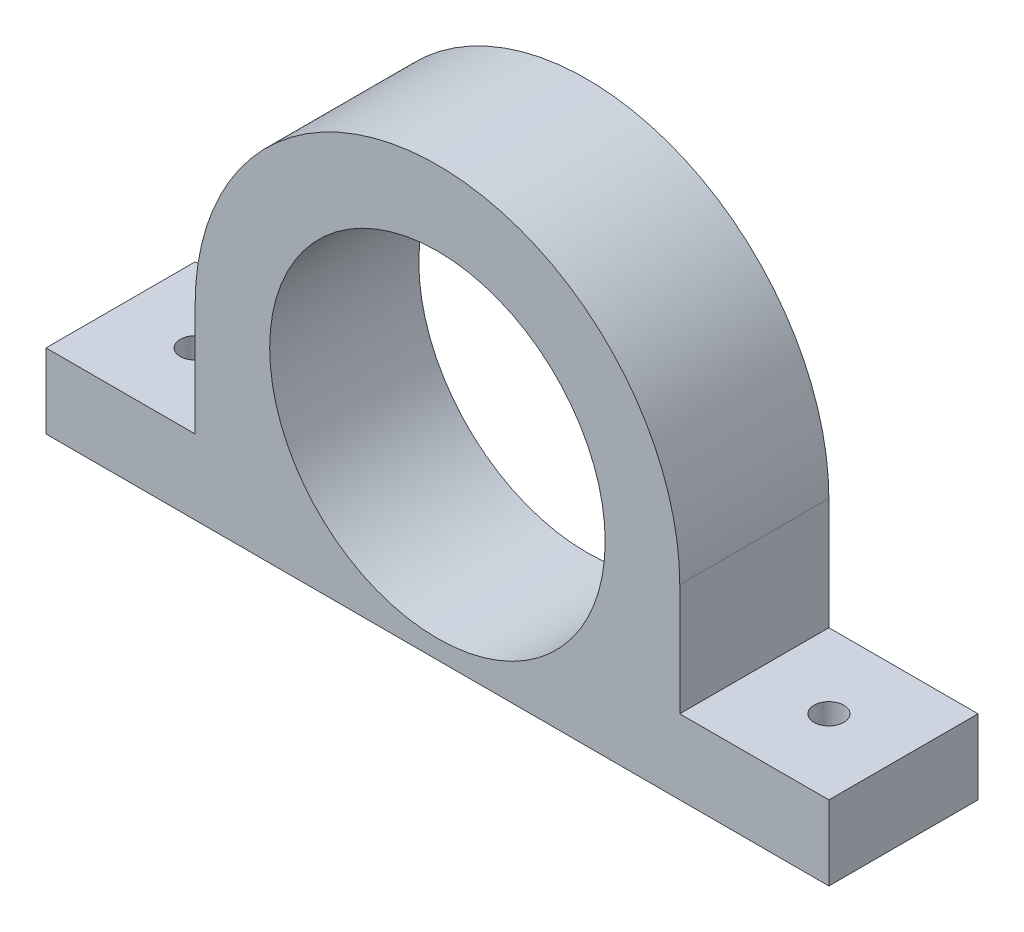
SolidWorks part; units mm, degrees
material "20% infill ABS"
ref_plane "Front Plane" through (0, 0, 0) normal (0, 0, 1) x (1, 0, 0)
ref_plane "Top Plane" through (0, 0, 0) normal (0, 1, 0) x (1, 0, 0)
ref_plane "Right Plane" through (0, 0, 0) normal (1, 0, 0) x (0, 0, -1)
sketch "Sketch1" plane through (0, 0, -167.5) normal (0, 0, 1) x (1, 0, 0)
  line L0 (-32.5, 0) -> (-32.5, -15)
  line L1 (-32.5, -15) -> (-52.5, -15)
  line L2 (-52.5, -15) -> (-52.5, -25)
  line L4 (-52.5, -25) -> (52.5, -25)
  line L5 (52.5, -25) -> (52.5, -15)
  line L6 (52.5, -15) -> (32.5, -15)
  line L7 (32.5, -15) -> (32.5, 0)
  arc A2 (-32.5, 0) -> (32.5, 0) centre (0, 0) cw
  circle A3 centre (0, 0) radius 22.5
  point P16 (0, 32.5)
  dimension "D3" = 10
  dimension "D2" = 45
  dimension "D1" = 10
  dimension "D4" = 20
  dimension "D5" = 2.5
extrude "Boss-Extrude2" add sketch "Sketch1" against normal blind 20
hole_wizard "Ø4.0mm Dowel Hole1" positions "Sketch2" profile "Sketch4" hole size "Ø4.0" standard "ANSI Metric" end condition through all
sketch "Sketch2" plane through (0, -15, 0) normal (0, 1, 0) x (1, 0, 0)
  line L0 (52.5, 187.5) -> (52.5, 167.5) construction
  line L1 (52.5, 187.5) -> (32.5, 187.5) construction
  line L2 (-52.5, 187.5) -> (-52.5, 167.5) construction
  line L3 (-32.5, 187.5) -> (-52.5, 187.5) construction
  point P0 (42.5, 177.5)
  point P2 (-42.5, 177.5)
  dimension "D1" = 10
  dimension "D2" = 10
  dimension "D3" = 10
  dimension "D4" = 10
sketch "Sketch4" plane through (42.5, -15, -177.5) normal (1, 0, 0) x (0, 0, 1)
  line L0 (0, 0) -> (0, 10)
  line L1 (0, 10) -> (2, 10)
  line L2 (2, 10) -> (2, 0)
  line L5 (2, 0) -> (0, 0)
  line L11 (0, -6.35) -> (0, 107.95) construction
  dimension "Thru Hole Dia." = 4
  dimension "Thru Hole Depth" = 10
